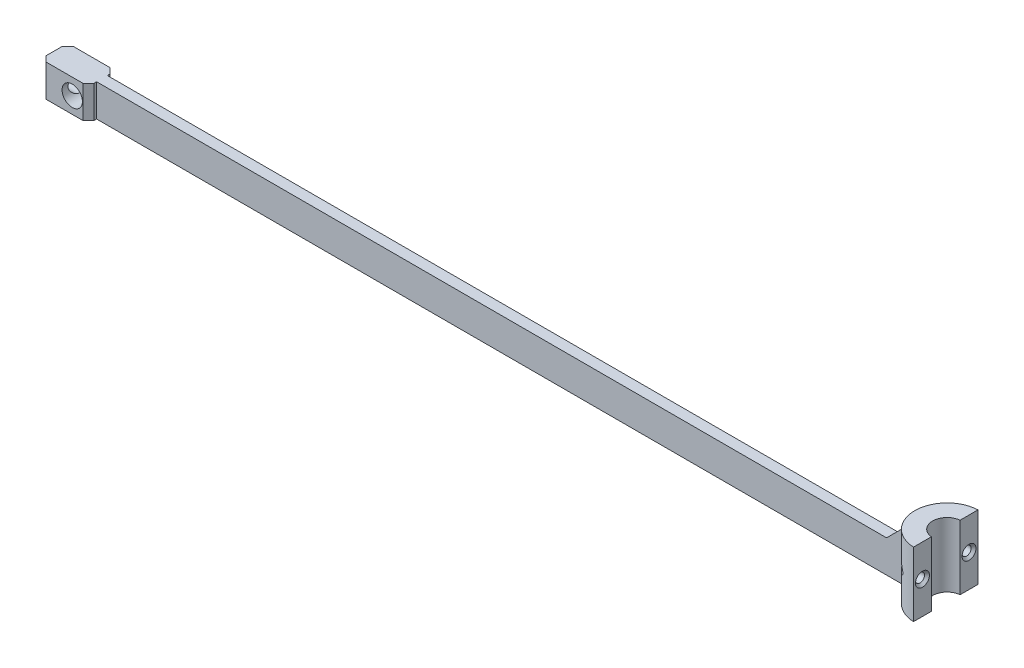
SolidWorks part; units mm, degrees
ref_plane "Front Plane" through (0, 0, 0) normal (0, 0, 1) x (1, 0, 0)
ref_plane "Top Plane" through (0, 0, 0) normal (0, 1, 0) x (1, 0, 0)
ref_plane "Right Plane" through (0, 0, 0) normal (1, 0, 0) x (0, 0, -1)
sketch "Sketch1" plane through (0, 0, 0) normal (0, 1, 0) x (1, 0, 0)
  line L1 (-127, -1.5875) -> (127, -1.5875)
  line L2 (-127, -1.5875) -> (-127, 1.5875)
  line L3 (-127, 1.5875) -> (127, 1.5875)
  line L4 (127, -1.5875) -> (127, 1.5875)
  line L5 (-127, -1.5875) -> (127, 1.5875) construction
  line L6 (-127, 1.5875) -> (127, -1.5875) construction
  point P0 (0, 0)
  dimension "D1" = 3.175
  dimension "D2" = 254
extrude "Boss-Extrude1" add sketch "Sketch1" along normal blind 9.525
sketch "Sketch2" plane through (0, 0, 0) normal (0, 1, 0) x (1, 0, 0)
  line L0 (127, -1.5875) -> (127, 1.5875) construction
  line L1 (126.6031, 9.5167) -> (126.6031, -9.5167)
  arc A0 (126.6031, 9.5167) -> (126.6031, -9.5167) centre (127, 0) ccw
  dimension "D1" = 19.05
  dimension "D2" = 0.3969
extrude "Boss-Extrude2" add sketch "Sketch2" along normal blind 19.05
sketch "Sketch3" plane through (0, 19.05, 0) normal (0, 1, 0) x (1, 0, 0)
  line L0 (127, -1.5875) -> (127, 1.5875) construction
  circle A0 centre (127, 0) radius 4.25
  dimension "D1" = 8.5
extrude "Cut-Extrude1" cut sketch "Sketch3" against normal through all
sketch "Sketch4" plane through (0, 0, 0) normal (0, 0, 1) x (1, 0, 0)
  line L0 (-127, 9.525) -> (-127, 0) construction
  line L1 (-127, 9.525) -> (117.6082, 9.525) construction
  line L2 (-131.7625, 0) -> (-122.2375, 0)
  line L3 (-131.7625, 0) -> (-131.7625, 9.525)
  line L4 (-131.7625, 9.525) -> (-122.2375, 9.525)
  line L5 (-122.2375, 0) -> (-122.2375, 9.525)
  line L6 (-131.7625, 0) -> (-122.2375, 9.525) construction
  line L7 (-131.7625, 9.525) -> (-122.2375, 0) construction
  circle A0 centre (-127, 4.7625) radius 3 construction
  dimension "D1" = 6
extrude "Boss-Extrude3" add sketch "Sketch4" along normal mid plane 8
sketch "Sketch5" plane through (0, 0, 4) normal (0, 0, 1) x (1, 0, 0)
  circle A0 centre (-127, 4.7625) radius 3 construction
  circle A1 centre (-127, 4.7625) radius 3
extrude "Cut-Extrude2" cut sketch "Sketch5" against normal through all draft 0.5 draft outward yes
sketch "Sketch6" plane through (0, 0, 4) normal (0, 0, 1) x (1, 0, 0)
  line L0 (-128.5, 7.3606) -> (-128.5, 2.1644)
  circle A0 centre (-127, 4.7625) radius 3 construction
  arc A1 (-128.5, 7.3606) -> (-128.5, 2.1644) centre (-127, 4.7625) ccw
  dimension "D1" = 4.5
sketch "Sketch7" plane through (0, 0, 0) normal (0, 0, 1) x (1, 0, 0)
  line L0 (110.7398, 9.525) -> (117.475, 16.2602)
  line L1 (-122.2375, 9.525) -> (117.6082, 9.525) construction
  line L2 (117.475, 19.05) -> (117.475, 9.525) construction
  dimension "D1" = 45
  dimension "D2" = 9.525
rib "Rib1" sketch "Sketch7" sketch "Sketch7" thickness 3.175 extrusion direction parallel to sketch draft on no parameters "D1"=3.175
other "Move Face1" face at (-131.7625, 4.7625, 0) offset 4.572 parameters "D1"=4.572
hole_wizard "#10-24 Tapped Hole1" positions "Sketch12" profile "Sketch11" tap size "#10-24" standard "ANSI Inch"
sketch "Sketch12" plane through (-136.3345, 0, 0) normal (-1, 0, 0) x (0, 0, 1)
  line L1 (4, 9.525) -> (4, 0) construction
  point P10 (0, 4.7625)
  point P16 (4, 4.7625)
  point P18 (0, 0)
sketch "Sketch11" plane through (-136.3345, 4.7625, 0) normal (0, 1, 0) x (0, 0, 1)
  line L0 (0, 0) -> (0, 10.7071)
  line L1 (0, 10.7071) -> (2.286, 9.3335)
  line L2 (2.286, 9.3335) -> (2.286, 0.762)
  line L3 (2.286, 0.762) -> (3.048, 0)
  line L5 (3.048, 0) -> (0, 0)
  line L6 (-2.286, 0.762) -> (-3.048, 0) construction
  line L10 (0, 10.7071) -> (-2.286, 9.3335) construction
  line L11 (0, -6.35) -> (0, 107.95) construction
  dimension "Tap Drill Dia." = 4.572
  dimension "Tap Drill Depth" = 9.3335
  dimension "Near C'Sink Dia." = 6.096
  dimension "Near C'Sink Angle" = 90
  dimension "Drill Angle" = 118
cosmetic thread "Hole Thread1" parameters "D1"=9.652, "D2"=4.826
hole_wizard "#4-40 Tapped Hole1" positions "Sketch13" profile "Sketch14" tap size "#4-40" standard "ANSI Inch"
sketch "Sketch13" plane through (126.6031, 0, 0) normal (1, 0, 0) x (0, 0, -1)
  line L4 (-9.5167, 0) -> (-4.2314, 19.05) construction
  line L6 (0, 22.3268) -> (0, -4.6692) construction
  point P0 (-6.8741, 9.525)
  point P17 (-6.8741, 9.525)
  point P22 (6.8741, 9.525)
sketch "Sketch14" plane through (126.6031, 9.525, 6.8741) normal (0, 1, 0) x (0, 0, -1)
  line L0 (0, 0) -> (0, 9.9304)
  line L1 (0, 9.9304) -> (1.3335, 9.1291)
  line L2 (1.3335, 9.1291) -> (1.3335, 0.7239)
  line L3 (1.3335, 0.7239) -> (2.0574, 0)
  line L5 (2.0574, 0) -> (0, 0)
  line L6 (-1.3335, 0.7239) -> (-2.0574, 0) construction
  line L10 (0, 9.9304) -> (-1.3335, 9.1291) construction
  line L11 (0, -6.35) -> (0, 107.95) construction
  dimension "Tap Drill Dia." = 2.667
  dimension "Tap Drill Depth" = 9.1291
  dimension "Near C'Sink Dia." = 4.1148
  dimension "Near C'Sink Angle" = 90
  dimension "Drill Angle" = 118
cosmetic thread "Hole Thread2" parameters "D1"=5.6896, "D2"=2.8448
cosmetic thread "Hole Thread3" parameters "D1"=5.6896, "D2"=2.8448
chamfer "Chamfer1" distance 1.5875 angle 45 6 edges at (117.6082, 8.1967, -1.5875) (117.6082, 8.1967, 1.5875) (-122.2375, 4.7625, -4) (-136.3345, 4.7625, -4) (-122.2375, 4.7625, 4) (-136.3345, 4.7625, 4) first distance on face at (20.2963, 7.0887, -1.5875) first distance on face at (20.2963, 7.0887, 1.5875) first distance on face at (-130.0698, 4.7625, -4) first distance on face at (-124, 4.7625, 4)
equation "\"draft\"= 0.5"
equation "\"D3@Cut-Extrude2\"= \"draft\""
equation "\"D3\" = \"draft\""
